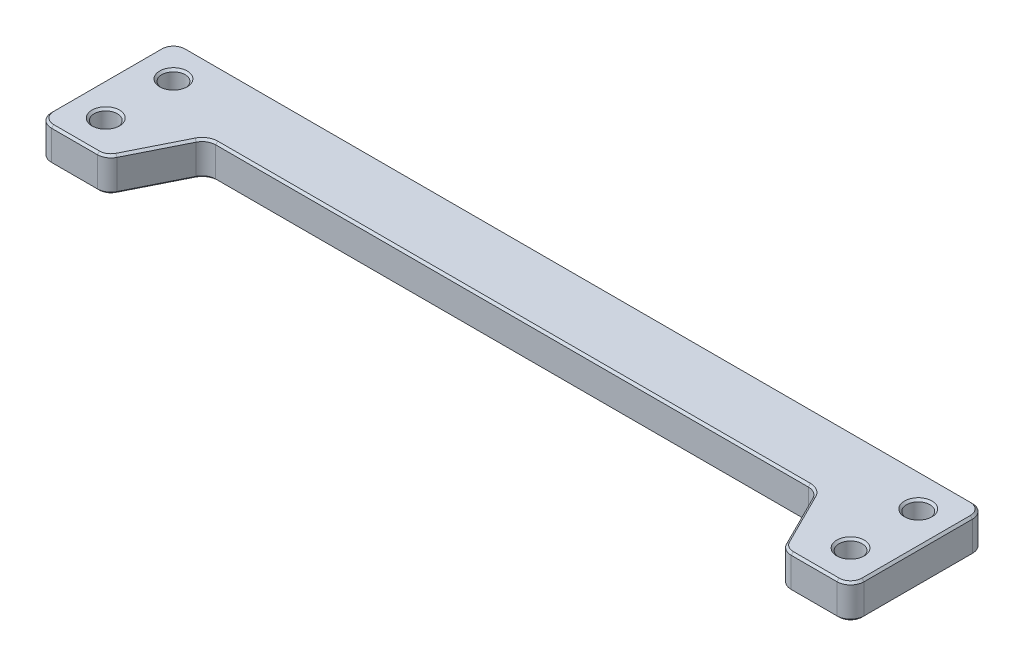
SolidWorks part; units mm, degrees
ref_plane "Front Plane" through (0, 0, 0) normal (0, 0, 1) x (1, 0, 0)
ref_plane "Top Plane" through (0, 0, 0) normal (0, 1, 0) x (1, 0, 0)
ref_plane "Right Plane" through (0, 0, 0) normal (1, 0, 0) x (0, 0, -1)
sketch "Sketch1" plane through (0, 0, 0) normal (0, 1, 0) x (1, 0, 0)
  line L0 (-3.81, 19.05) -> (143.51, 19.05)
  line L1 (146.05, 16.51) -> (146.05, -3.81)
  line L2 (143.51, -6.35) -> (134.9198, -6.35)
  line L3 (132.648, -4.9459) -> (127.702, 4.9459)
  line L4 (125.4302, 6.35) -> (14.2698, 6.35)
  line L5 (11.998, 4.9459) -> (7.052, -4.9459)
  line L6 (4.7802, -6.35) -> (-3.81, -6.35)
  line L7 (-6.35, -3.81) -> (-6.35, 16.51)
  circle A0 centre (0, 0) radius 2.1828
  circle A1 centre (0, 12.7) radius 2.1828
  circle A2 centre (139.7, 12.7) radius 2.1828
  circle A3 centre (139.7, 0) radius 2.1828
  arc A4 (127.702, 4.9459) -> (125.4302, 6.35) centre (125.4302, 3.81) ccw
  arc A5 (134.9198, -6.35) -> (132.648, -4.9459) centre (134.9198, -3.81) cw
  arc A6 (146.05, -3.81) -> (143.51, -6.35) centre (143.51, -3.81) cw
  arc A7 (143.51, 19.05) -> (146.05, 16.51) centre (143.51, 16.51) cw
  arc A8 (-3.81, -6.35) -> (-6.35, -3.81) centre (-3.81, -3.81) cw
  arc A9 (-3.81, 19.05) -> (-6.35, 16.51) centre (-3.81, 16.51) ccw
  arc A10 (14.2698, 6.35) -> (11.998, 4.9459) centre (14.2698, 3.81) ccw
  arc A11 (7.052, -4.9459) -> (4.7802, -6.35) centre (4.7802, -3.81) cw
  point P19 (127, 6.35)
  point P22 (133.35, -6.35)
  point P25 (146.05, -6.35)
  point P34 (12.7, 6.35)
  point P37 (6.35, -6.35)
  dimension "D1" = 139.7
  dimension "D3" = 4.3656
  dimension "D4" = 4.3656
  dimension "D5" = 4.3656
  dimension "D6" = 4.3656
  dimension "D17" = 2.54
  dimension "D2" = 12.7
  dimension "D7" = 6.35
  dimension "D8" = 6.35
  dimension "D9" = 6.35
  dimension "D10" = 6.35
  dimension "D11" = 6.35
  dimension "D12" = 12.7
  dimension "D13" = 6.35
  dimension "D14" = 6.35
  dimension "D15" = 6.35
  dimension "D16" = 6.35
extrude "Boss-Extrude1" add sketch "Sketch1" along normal blind 6.35
chamfer "Chamfer1" distance 0.3969 angle 45 40 edges at (139.7, 0, 2.1828) (139.7, 0, -10.5172) (0, 0, -10.5172) (0, 0, 2.1828) (130.175, 0, 0) (133.5844, 0, 5.9707) (139.2149, 0, 6.35) (145.3061, 0, 5.6061) (146.05, 0, -6.35) (145.3061, 0, -18.3061) (69.85, 0, -19.05) (-5.6061, 0, -18.3061) (-6.35, 0, -6.35) (-5.6061, 0, 5.6061) (0.4851, 0, 6.35) (6.1156, 0, 5.9707) (9.525, 0, 0) (12.9344, 0, -5.9707) (69.85, 0, -6.35) (126.7656, 0, -5.9707) (139.7, 6.35, 2.1828) (0, 6.35, -10.5172) (69.85, 6.35, -6.35) (12.9344, 6.35, -5.9707) (9.525, 6.35, 0) (6.1156, 6.35, 5.9707) (0.4851, 6.35, 6.35) (-5.6061, 6.35, 5.6061) (-6.35, 6.35, -6.35) (-5.6061, 6.35, -18.3061) (69.85, 6.35, -19.05) (145.3061, 6.35, -18.3061) (146.05, 6.35, -6.35) (145.3061, 6.35, 5.6061) (139.2149, 6.35, 6.35) (133.5844, 6.35, 5.9707) (130.175, 6.35, 0) (126.7656, 6.35, -5.9707) (0, 6.35, 2.1828) (139.7, 6.35, -10.5172)
